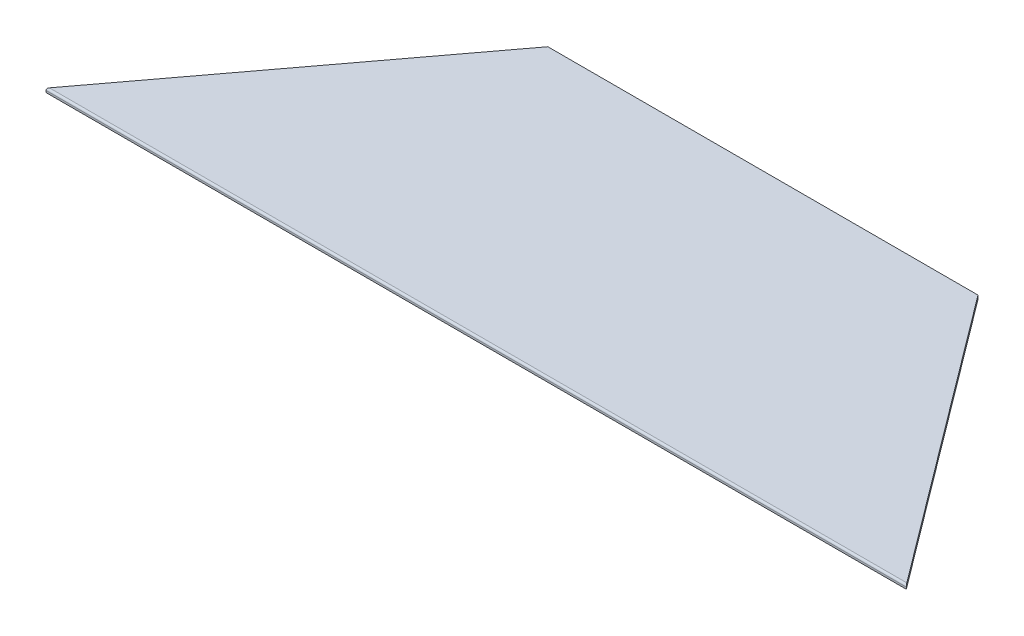
SolidWorks part; units mm, degrees
ref_plane "Front Plane" through (0, 0, 0) normal (0, 0, 1) x (1, 0, 0)
ref_plane "Top Plane" through (0, 0, 0) normal (0, 1, 0) x (1, 0, 0)
ref_plane "Right Plane" through (0, 0, 0) normal (1, 0, 0) x (0, 0, -1)
sketch "Sketch1" plane through (0, 0, 0) normal (0, 1, 0) x (1, 0, 0)
  line L0 (228.6, 0) -> (228.6, 152.4) construction
  line L1 (0, 0) -> (457.2, 0)
  line L3 (114.3, 152.4) -> (342.9, 152.4)
  line L5 (228.6, 152.4) -> (342.9, 152.4) construction
  line L6 (228.6, 152.4) -> (114.3, 152.4) construction
  line L7 (114.3, 152.4) -> (0, 0)
  line L8 (342.9, 152.4) -> (457.2, 0)
  point P7 (0, 0)
extrude "Boss-Extrude1" add sketch "Sketch1" along normal blind 2.0574
fillet "Fillet1" radius 1.0287 1 edges at (228.6, 2.0574, 0)
